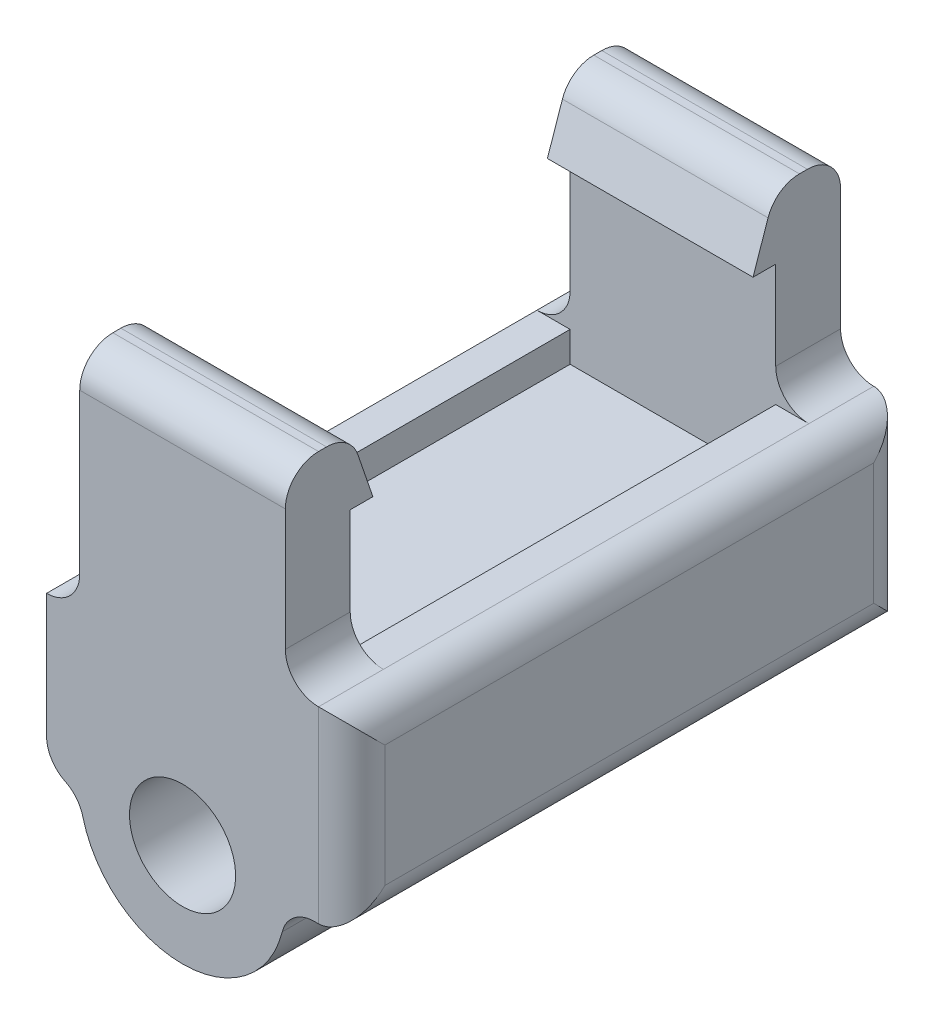
SolidWorks part; units mm, degrees
material "ABS"
ref_plane "Plano frontal" through (0, 0, 0) normal (0, 0, 1) x (1, 0, 0)
ref_plane "Plano superior" through (0, 0, 0) normal (0, 1, 0) x (1, 0, 0)
ref_plane "Plano direito" through (0, 0, 0) normal (1, 0, 0) x (0, 0, -1)
sketch "Esboço1" plane through (0, 0, 0) normal (0, 0, 1) x (1, 0, 0)
  circle A0 centre (16.0167, 16.0167) radius 3.1
  circle A1 centre (16.0167, 16.0167) radius 1.55
  dimension "D1" = 3.1
extrude "Ressalto-extrusão1" add sketch "Esboço1" along normal up to vertex (16.74 mm away)
sketch "Sketch1" plane through (0, 0, 0) normal (0, 0, -1) x (-1, 0, 0)
  line L2 (-12.9167, 16.0167) -> (-12.9167, 19.6347)
  line L3 (-12.9167, 19.6347) -> (-19.1167, 19.6347)
  line L4 (-19.1167, 16.0167) -> (-19.1167, 19.6347)
  circle A0 centre (-16.0167, 16.0167) radius 3.1 construction
  arc A1 (-12.9167, 16.0167) -> (-19.1167, 16.0167) centre (-16.0167, 16.0167) ccw
extrude "Boss-Extrude1" add sketch "Sketch1" against normal up to surface (16.74 mm away) up to face at (19.1167, 16.0167, 16.74)
sketch "Sketch2" plane through (0, 19.6347, 0) normal (0, 1, 0) x (1, 0, 0)
  line L0 (19.1167, -16.74) -> (19.1167, 0) construction
  line L1 (12.9167, 0) -> (19.1167, 0)
  line L2 (12.9167, 0) -> (12.9167, -1.955)
  line L3 (12.9167, -1.955) -> (19.1167, -1.955)
  line L4 (19.1167, 0) -> (19.1167, -1.955)
  line L6 (19.1167, -14.785) -> (12.9167, -14.785)
  line L7 (19.1167, -14.785) -> (19.1167, -16.74)
  line L8 (19.1167, -16.74) -> (12.9167, -16.74)
  line L9 (12.9167, -14.785) -> (12.9167, -16.74)
extrude "Boss-Extrude2" add sketch "Sketch2" along normal offset from surface (7.715 mm away) 2
sketch "Sketch4" plane through (12.9167, 0, 0) normal (-1, 0, 0) x (0, 0, 1)
  line L0 (1.955, 27.3497) -> (1.955, 25.3497)
  line L1 (1.955, 25.3497) -> (2.6393, 25.3497)
  line L2 (2.6393, 25.3497) -> (1.955, 27.3497)
  line L3 (8.37, 25.3497) -> (8.37, 25.0062) construction
  line L4 (14.1007, 25.3497) -> (14.785, 27.3497)
  line L5 (14.785, 25.3497) -> (14.1007, 25.3497)
  line L6 (14.785, 27.3497) -> (14.785, 25.3497)
extrude "Boss-Extrude3" add sketch "Sketch4" against normal up to surface (6.2 mm away) up to face at (19.1167, 23.0699, 9.1719)
sketch "Sketch5" plane through (19.1167, 0, 0) normal (1, 0, 0) x (0, 0, -1)
  line L0 (-16.74, 16.0167) -> (0, 16.0167) construction
  line L1 (-16.74, 16.0167) -> (0, 16.0167)
  line L2 (-16.74, 16.0167) -> (-16.74, 21.6832)
  line L3 (-16.74, 21.6832) -> (0, 21.6832)
  line L4 (0, 16.0167) -> (0, 21.6832)
  line L5 (-16.74, 16.0167) -> (-16.74, 12.9167) construction
  line L6 (0, 27.3497) -> (0, 16.0167) construction
extrude "Boss-Extrude4" add sketch "Sketch5" along normal blind 2
sketch "Sketch6" plane through (12.9167, 0, 0) normal (-1, 0, 0) x (0, 0, 1)
  line L0 (0, 16.0167) -> (0, 12.9167) construction
  line L1 (0, 16.0167) -> (16.74, 16.0167)
  line L2 (0, 16.0167) -> (0, 20.5461)
  line L3 (0, 20.5461) -> (16.74, 20.5461)
  line L4 (16.74, 16.0167) -> (16.74, 20.5461)
  line L5 (0, 16.0167) -> (0, 27.3497) construction
  line L6 (16.74, 16.0167) -> (16.74, 27.3497) construction
extrude "Boss-Extrude5" add sketch "Sketch6" along normal blind 1
fillet "Fillet1" radius 1 14 edges at (21.1167, 21.6832, 8.37) (21.1167, 18.8499, 0) (21.1167, 16.0167, 8.37) (21.1167, 18.8499, 16.74) (16.0167, 27.3497, 0) (16.0167, 27.3497, 1.955) (16.0167, 27.3497, 16.74) (16.0167, 27.3497, 14.785) (19.1167, 21.6832, 15.7625) (12.9167, 20.5461, 15.7625) (12.9167, 20.5461, 0.9775) (19.1167, 21.6832, 0.9775) (12.9167, 16.0167, 8.37) (19.1167, 16.0167, 8.37)
fillet "Fillet4" radius 1 1 edges at (11.9167, 16.0167, 8.37)
hole_wizard "M3 Clearance Hole1" positions "Sketch8" profile "Sketch7" hole size "M3" standard "ISO" end condition through all
sketch "Sketch8" plane through (0, 0, 0) normal (0, 0, -1) x (-1, 0, 0)
  point P0 (-16.0167, 16.0167)
sketch "Sketch7" plane through (16.0167, 16.0167, 0) normal (1, 0, 0) x (0, 1, 0)
  line L0 (0, 0) -> (0, 16.74)
  line L1 (0, 16.74) -> (1.6, 16.74)
  line L2 (1.6, 16.74) -> (1.6, 0)
  line L5 (1.6, 0) -> (0, 0)
  line L11 (0, -6.35) -> (0, 107.95) construction
  dimension "Thru Hole Dia." = 3.2
  dimension "Thru Hole Depth" = 16.74
